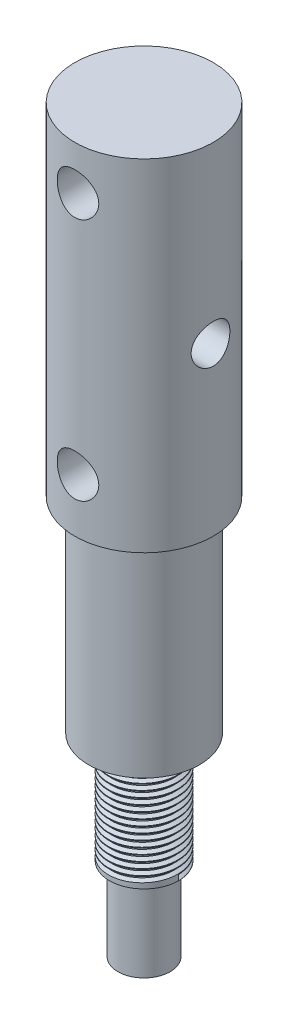
SolidWorks part; units mm, degrees
material "AISI 316 Annealed Stainless Steel Bar (SS)"
ref_plane "Front Plane" through (0, 0, 0) normal (0, 0, 1) x (1, 0, 0)
ref_plane "Top Plane" through (0, 0, 0) normal (0, 1, 0) x (1, 0, 0)
ref_plane "Right Plane" through (0, 0, 0) normal (1, 0, 0) x (0, 0, -1)
sketch "Sketch2" plane through (0, 0, 0) normal (0, 0, 1) x (1, 0, 0)
  line L0 (0, 0) -> (0, 508.8276) construction
  line L1 (0, 0) -> (6, 0)
  line L2 (0, 0) -> (0, 19.05)
  line L3 (0, 19.05) -> (6, 19.05)
  line L4 (6, 0) -> (6, 19.05)
  line L5 (0, 19.05) -> (7.9375, 19.05)
  line L6 (0, 19.05) -> (0, 44.45)
  line L7 (0, 44.45) -> (7.9375, 44.45)
  line L8 (7.9375, 19.05) -> (7.9375, 44.45)
  line L9 (0, 44.45) -> (12.721, 44.45)
  line L10 (0, 44.45) -> (0, 91.44)
  line L11 (0, 91.44) -> (12.721, 91.44)
  line L12 (12.721, 44.45) -> (12.721, 91.44)
  line L13 (0, 91.44) -> (15.875, 91.44)
  line L14 (0, 91.44) -> (0, 169.672)
  line L15 (0, 169.672) -> (15.875, 169.672)
  line L16 (15.875, 91.44) -> (15.875, 169.672)
  dimension "D1" = 78.232
  dimension "D2" = 15.875
  dimension "D4" = 46.99
  dimension "D3" = 12.721
  dimension "D5" = 25.4
  dimension "D6" = 7.9375
  dimension "D7" = 19.05
  dimension "D8" = 6
revolve "Revolve1" add sketch "Sketch2" angle 360 about L0 region at (3, 9.525, 0) region at (3.9687, 31.75, 0) region at (6.3605, 67.945, 0) region at (7.9375, 130.556, 0)
thread "Thread2" pitch 1.4111 method cut profile "Thread Profile3" start angle 0, offset 0, length 0, pitch 1.4111, diameter 15.875
ref_plane "Plane3" through (7.9375, 19.05, 0) normal (0, 0, 1) x (1, 0, 0)
sketch "Thread Profile3" plane through (7.9375, 19.05, 0) normal (0, 0, 1) x (1, 0, 0)
  line L0 (0, 0) -> (0, 1.4111) construction
  line L11 (0, 0) -> (0, 1.2347)
  line L12 (0, 1.2347) -> (-0.7638, 0.7937)
  line L13 (-0.7638, 0.7937) -> (-0.7638, 0.441)
  line L15 (-0.7638, 0.441) -> (0, 0)
  line L17 (-0.7638, 0.6174) -> (0, 0.6174) construction
  point P2 (0, 0)
  dimension "Pitch" = 1.4111
  dimension "Profile_Angle" = 60
  dimension "Profile_Land" = 0.3528
  dimension "Profile_Height" = 0.7638
sketch "Sketch3" plane through (0, 0, 0) normal (0, 0, 1) x (1, 0, 0)
  line L0 (0, 0) -> (0, 197.3408) construction
  line L1 (15.875, 169.672) -> (-15.875, 169.672) construction
  circle A0 centre (0, 159.512) radius 4.7625
  circle A1 centre (0, 103.632) radius 4.7625
  dimension "D1" = 9.525
  dimension "D2" = 10.16
  dimension "D3" = 66.04
extrude "Cut-Extrude1" cut sketch "Sketch3" against normal through all both and the other way through all
sketch "Sketch6" plane through (0, 0, 0) normal (1, 0, 0) x (0, 0, -1)
  line L0 (15.875, 169.672) -> (-15.875, 169.672) construction
  circle A0 centre (0, 129.667) radius 4.445
  point P4 (0, 0)
  dimension "D2" = 8.89
  dimension "D1" = 40.005
extrude "Cut-Extrude2" cut sketch "Sketch6" against normal through all both and the other way through all
equation "\"hole diamiter\" = 1.25in"
equation "\"wheel depth\"= 2.88"
equation "\"press_tolerance\"= 0.00165"
equation "\"wheel_connection\"= \"hole diamiter\"'https://at-machining.com/tolerance-press-fit/"
equation "\"D1@Sketch2\"=\"wheel depth\"+0.2"
equation "\"D2@Sketch2\"=\"wheel_connection\"/2"
equation "\"fitting depth\"= 1.85"
equation "\"D4@Sketch2\"=\"fitting depth\""
equation "\"bearing_id\"= 1"
equation "\"bearing_connection\"= \"bearing_id\" + \"press_tolerance\"'https://at-machining.com/tolerance-press-fit/"
equation "\"D3@Sketch2\"=\"bearing_connection\"/2"
equation "\"thread length\"= 1"
equation "\"major_diamiter\"= 5 / 8'https://www.machiningdoctor.com/threadinfo/?tid=81"
equation "\"D5@Sketch2\"=\"thread length\""
equation "\"D6@Sketch2\"=\"major_diamiter\"/2"
equation "\"coupling diamiter\"= 12mm"
equation "\"coupling lenght\"= 1.5 / 2"
equation "\"D7@Sketch2\"=\"coupling lenght\""
equation "\"D8@Sketch2\"=\"coupling diamiter\"/2"
equation "\"hub_spacing\" = .5"
equation "\"D2@Sketch9\"=\"hub_spacing\""
